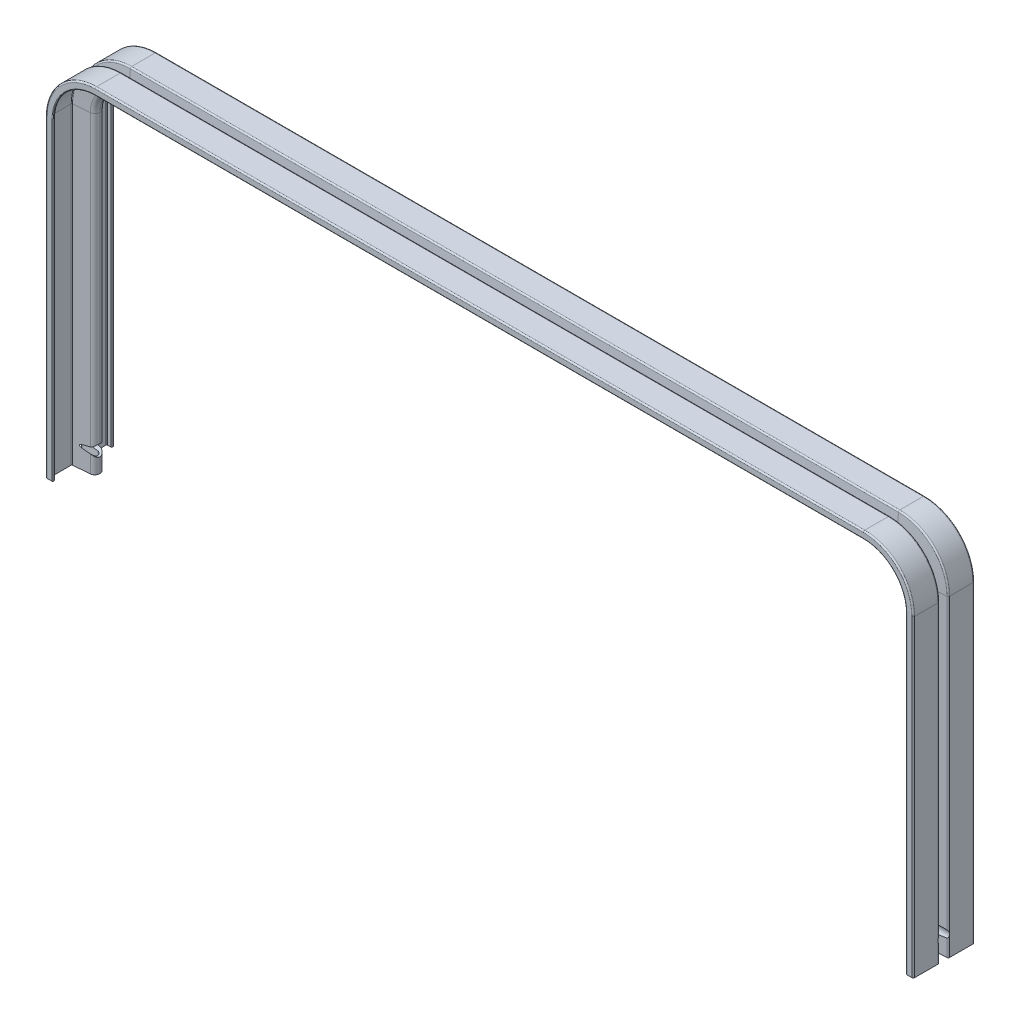
SolidWorks part; units mm, degrees
material "AISI 1020 Acero laminado en frío"
ref_plane "Alzado" through (0, 0, 0) normal (0, 0, 1) x (1, 0, 0)
ref_plane "Planta" through (0, 0, 0) normal (0, 1, 0) x (1, 0, 0)
ref_plane "Vista lateral" through (0, 0, 0) normal (1, 0, 0) x (0, 0, -1)
sketch "Croquis2" plane through (0, 0, 0) normal (1, 0, 0) x (0, 0, -1)
  line L4 (2, -2) -> (-2, -2) construction
  line L5 (21.5, 12) -> (-21.5, 12) construction
  line L8 (-3.5977, -0.2791) -> (-2.1024, -0.1595) construction
  line L9 (0, -3.5) -> (0, 12) construction
  line L10 (-3.0048, 11.1196) -> (-2.9952, 11)
  line L11 (-5.8278, 10.3021) -> (-7.826, 10.3021) construction
  line L12 (-5.8278, 10.3021) -> (-5.8278, 13.2411) construction
  line L13 (-5.8278, 13.2411) -> (-20.5, 13.2411)
  line L14 (-21.5, 12.2411) -> (-21.5, 8.7411)
  line L15 (-21, 8.2411) -> (-20.5, 8.2411)
  line L16 (-20, 8.7411) -> (-20, 11.2411)
  line L17 (-19.5, 11.7411) -> (-5.8278, 11.7411)
  line L18 (-4.5, 11) -> (-4.9298, 10.9656) construction
  line L19 (-4.5, 11) -> (-4.5881, 12.1007) construction
  line L20 (-5.8278, 11.7411) -> (-4.3336, 11.7411) construction
  line L21 (-4.5, 11) -> (-4.5225, 11.281)
  line L22 (-5.0209, 11.7411) -> (-5.8278, 11.7411)
  line L23 (-2.9952, 11) -> (-3.0048, 11.1196)
  line L24 (-3.0048, 11.1196) -> (-3.1009, 12.3209)
  line L25 (-5.8278, 13.2411) -> (-4.0977, 13.2411)
  line L26 (0.1088, -3.5) -> (-0.1088, -3.5)
  line L27 (-3.5977, -0.2791) -> (-4.5, 11)
  line L28 (-1.2335, -2) -> (-1.103, -2.2764) construction
  line L29 (-2.5488, 5.4203) -> (-1.7472, -4.6) construction
  line L30 (-1.236, -2) -> (-1.2335, -2)
  line L31 (-2.1024, -0.1595) -> (-2.9952, 11)
  line L32 (0.1088, -2) -> (-0.1088, -2)
  line L33 (-2.1024, -0.1595) -> (-2.9952, 11)
  line L34 (2.5488, 5.4203) -> (1.7472, -4.6) construction
  line L35 (1.2335, -2) -> (1.103, -2.2764) construction
  line L36 (5.8278, 11.7411) -> (4.3336, 11.7411) construction
  line L37 (4.5, 11) -> (4.5881, 12.1007) construction
  line L38 (4.5, 11) -> (4.9298, 10.9656) construction
  line L39 (5.8278, 10.3021) -> (5.8278, 13.2411) construction
  line L40 (5.8278, 10.3021) -> (7.826, 10.3021) construction
  line L41 (3.5977, -0.2791) -> (2.1024, -0.1595) construction
  line L42 (2.1024, -0.1595) -> (2.9952, 11)
  line L43 (2.1024, -0.1595) -> (2.9952, 11)
  line L44 (1.236, -2) -> (1.2335, -2)
  line L45 (3.5977, -0.2791) -> (4.5, 11)
  line L46 (5.8278, 13.2411) -> (4.0977, 13.2411)
  line L47 (3.0048, 11.1196) -> (3.1009, 12.3209)
  line L48 (2.9952, 11) -> (3.0048, 11.1196)
  line L49 (5.0209, 11.7411) -> (5.8278, 11.7411)
  line L50 (4.5, 11) -> (4.5225, 11.281)
  line L51 (19.5, 11.7411) -> (5.8278, 11.7411)
  line L52 (20, 8.7411) -> (20, 11.2411)
  line L53 (21, 8.2411) -> (20.5, 8.2411)
  line L54 (21.5, 12.2411) -> (21.5, 8.7411)
  line L55 (5.8278, 13.2411) -> (20.5, 13.2411)
  line L56 (3.0048, 11.1196) -> (2.9952, 11)
  arc A0 (-2.1024, -0.1595) -> (-0.1088, -2) centre (-0.1088, 0) ccw
  arc A1 (3.5977, -0.2791) -> (0.1088, -3.5) centre (0.1088, 0) cw
  arc A4 (-5.0209, 11.7411) -> (-4.5225, 11.281) centre (-5.0209, 11.2411) cw
  arc A5 (-3.1009, 12.3209) -> (-4.0977, 13.2411) centre (-4.0977, 12.2411) ccw
  arc A6 (-20, 11.2411) -> (-19.5, 11.7411) centre (-19.5, 11.2411) cw
  arc A7 (-20.5, 13.2411) -> (-21.5, 12.2411) centre (-20.5, 12.2411) ccw
  arc A8 (-20, 8.7411) -> (-20.5, 8.2411) centre (-20.5, 8.7411) cw
  arc A9 (-21, 8.2411) -> (-21.5, 8.7411) centre (-21, 8.7411) cw
  arc A10 (-3.5977, -0.2791) -> (-0.1088, -3.5) centre (-0.1088, 0) ccw
  arc A11 (21, 8.2411) -> (21.5, 8.7411) centre (21, 8.7411) ccw
  arc A12 (20, 8.7411) -> (20.5, 8.2411) centre (20.5, 8.7411) ccw
  arc A13 (20.5, 13.2411) -> (21.5, 12.2411) centre (20.5, 12.2411) cw
  arc A14 (20, 11.2411) -> (19.5, 11.7411) centre (19.5, 11.2411) ccw
  arc A15 (3.1009, 12.3209) -> (4.0977, 13.2411) centre (4.0977, 12.2411) cw
  arc A16 (5.0209, 11.7411) -> (4.5225, 11.281) centre (5.0209, 11.2411) ccw
  arc A17 (2.1024, -0.1595) -> (0.1088, -2) centre (0.1088, 0) cw
  point P4 (0, 0)
  point P8 (0, 12)
  point P32 (-4.5593, 11.7411)
  point P49 (-1.9552, -2)
  point P88 (0, -2)
  point P90 (1.9552, -2)
  point P91 (4.5593, 11.7411)
  dimension "D3" = 3.5
  dimension "D8" = 1.5
  dimension "D9" = 0.5
  dimension "D11" = 1
  dimension "D12" = 1.361
  dimension "D13" = 0.5
  dimension "D14" = 1
  dimension "D15" = 0.5
  dimension "D5" = 2
  dimension "D6" = 2
  dimension "D10" = 1.5
  dimension "D16" = 21.5
extrude "Saliente-Extruir1" add sketch "Croquis2" along normal mid plane 540 contours L42 A17 L32 A0 L31 L10 L24 A5 L25 L13 A7 L14 A9 L15 A8 L16 A6 L17 L22 A4 L21 L27 A10 L26 A1 L45 L50 A16 L49 L51 A14 L52 A12 L53 A11 L54 A13 L55 L46 A15 L47 L48 region at (0, 11.023, 3.46)
sketch "Croquis4" plane through (0, 0, 0) normal (0, 0, 1) x (1, 0, 0)
  line L0 (0, -4.7328) -> (0, 13.2411) construction
  line L1 (270, 13.2411) -> (-270, 13.2411) construction
  line L2 (0, 115.1283) -> (-251.0425, 15.746)
  line L3 (-270, -12.1478) -> (-270, -232.1463)
  line L4 (270, -12.1478) -> (270, -232.1463)
  line L5 (0, 115.1283) -> (251.0425, 15.746)
  arc A0 (-251.0425, 15.746) -> (-270, -12.1478) centre (-240, -12.1478) ccw
  arc A1 (251.0425, 15.746) -> (270, -12.1478) centre (240, -12.1478) cw
  point P10 (-270, 8.2411)
  point P15 (270, 8.2411)
  dimension "D1" = 30
  dimension "D2" = 269.9985
  dimension "D3" = 219.9985
sketch "Croquis9" plane through (270, 0, 0) normal (1, 0, 0) x (0, 0, -1)
  line L0 (-19.5, 11.7411) -> (-5.0209, 11.7411)
  line L1 (-4.5225, 11.281) -> (-3.5977, -0.2791)
  line L2 (-3.1009, 12.3209) -> (-2.1024, -0.1595)
  line L3 (2.1024, -0.1595) -> (3.1009, 12.3209)
  line L4 (4.5225, 11.281) -> (3.5977, -0.2791)
  line L5 (4.0977, 13.2411) -> (20.5, 13.2411)
  line L6 (21.5, 12.2411) -> (21.5, 8.7411)
  line L7 (21, 8.2411) -> (20.5, 8.2411)
  line L8 (21, 8.2411) -> (20.5, 8.2411) construction
  line L9 (20, 8.7411) -> (20, 11.2411)
  line L10 (19.5, 11.7411) -> (5.0209, 11.7411)
  line L11 (-20, 11.2411) -> (-20, 8.7411)
  line L12 (-20.5, 8.2411) -> (-21, 8.2411)
  line L13 (-21.5, 8.7411) -> (-21.5, 12.2411)
  line L14 (-20.5, 13.2411) -> (-4.0977, 13.2411)
  line L15 (-0.1088, -2) -> (0.1088, -2)
  line L16 (-0.1088, -3.5) -> (0.1088, -3.5)
  line L17 (-0.1088, -21.7589) -> (18.9384, -21.7589) construction
  arc A0 (21, 8.2411) -> (21.5, 8.7411) centre (21, 8.7411) ccw construction
  arc A1 (-21, 8.2411) -> (-21.5, 8.7411) centre (-21, 8.7411) cw
  arc A2 (-21.5, 12.2411) -> (-20.5, 13.2411) centre (-20.5, 12.2411) cw
  arc A3 (-20, 11.2411) -> (-19.5, 11.7411) centre (-19.5, 11.2411) cw
  arc A4 (-5.0209, 11.7411) -> (-4.5225, 11.281) centre (-5.0209, 11.2411) cw
  arc A5 (-4.0977, 13.2411) -> (-3.1009, 12.3209) centre (-4.0977, 12.2411) cw
  arc A6 (-3.5977, -0.2791) -> (-0.1088, -3.5) centre (-0.1088, 0) ccw
  arc A7 (-2.1024, -0.1595) -> (-0.1088, -2) centre (-0.1088, 0) ccw
  arc A8 (2.1024, -0.1595) -> (0.1088, -2) centre (0.1088, 0) cw
  arc A9 (3.5977, -0.2791) -> (0.1088, -3.5) centre (0.1088, 0) cw
  arc A10 (3.1009, 12.3209) -> (4.0977, 13.2411) centre (4.0977, 12.2411) cw
  arc A11 (4.5225, 11.281) -> (5.0209, 11.7411) centre (5.0209, 11.2411) cw
  arc A12 (19.5, 11.7411) -> (20, 11.2411) centre (19.5, 11.2411) cw
  arc A13 (20.5, 13.2411) -> (21.5, 12.2411) centre (20.5, 12.2411) cw
  arc A14 (20, 8.7411) -> (20.5, 8.2411) centre (20.5, 8.7411) ccw
  arc A15 (21, 8.2411) -> (21.5, 8.7411) centre (21, 8.7411) ccw
  arc A16 (-20.5, 8.2411) -> (-20, 8.7411) centre (-20.5, 8.7411) ccw
  dimension "D1" = 30
revolve "Revolución1" add sketch "Croquis9" angle 90 about L17
mirror "Simetría1" about plane through (0, 0, 0) normal (1, 0, 0) of "Revolución1"
sketch "Croquis10" plane through (0, -21.7589, 0) normal (0, -1, 0) x (1, 0, 0)
  line L0 (300.5, 21.5) -> (304, 21.5)
  line L1 (305, 20.5) -> (305, 4.0977)
  line L2 (300, 20.5) -> (300, 21)
  line L3 (300.5, 20) -> (303, 20)
  line L4 (303.5, 19.5) -> (303.5, 5.0209)
  line L5 (303.0399, 4.5225) -> (291.4798, 3.5977)
  line L6 (304.0797, 3.1009) -> (291.5994, 2.1024)
  line L7 (288.2589, -0.1088) -> (288.2589, 0.1088)
  line L8 (289.7589, -0.1088) -> (289.7589, 0.1088)
  line L9 (291.5994, -2.1024) -> (304.0797, -3.1009)
  line L10 (291.4798, -3.5977) -> (303.0399, -4.5225)
  line L11 (303.5, -19.5) -> (303.5, -5.0209)
  line L12 (305, -4.0977) -> (305, -20.5)
  line L13 (303, -20) -> (300.5, -20)
  line L14 (304, -21.5) -> (300.5, -21.5)
  line L15 (300, -21) -> (300, -20.5)
  arc A0 (304, 21.5) -> (305, 20.5) centre (304, 20.5) cw
  arc A1 (300.5, 21.5) -> (300, 21) centre (300.5, 21) ccw
  arc A2 (300, 20.5) -> (300.5, 20) centre (300.5, 20.5) ccw
  arc A3 (303, 20) -> (303.5, 19.5) centre (303, 19.5) cw
  arc A4 (303.5, 5.0209) -> (303.0399, 4.5225) centre (303, 5.0209) cw
  arc A5 (305, 4.0977) -> (304.0797, 3.1009) centre (304, 4.0977) cw
  arc A6 (291.4798, 3.5977) -> (288.2589, 0.1088) centre (291.7589, 0.1088) ccw
  arc A7 (291.5994, 2.1024) -> (289.7589, 0.1088) centre (291.7589, 0.1088) ccw
  arc A8 (288.2589, -0.1088) -> (291.4798, -3.5977) centre (291.7589, -0.1088) ccw
  arc A9 (289.7589, -0.1088) -> (291.5994, -2.1024) centre (291.7589, -0.1088) ccw
  arc A10 (303.5, -5.0209) -> (303.0399, -4.5225) centre (303, -5.0209) ccw
  arc A11 (304.0797, -3.1009) -> (305, -4.0977) centre (304, -4.0977) cw
  arc A12 (305, -20.5) -> (304, -21.5) centre (304, -20.5) cw
  arc A13 (303, -20) -> (303.5, -19.5) centre (303, -19.5) ccw
  arc A14 (300.5, -21.5) -> (300, -21) centre (300.5, -21) cw
  arc A15 (300, -20.5) -> (300.5, -20) centre (300.5, -20.5) cw
extrude "Saliente-Extruir2" add sketch "Croquis10" along normal blind 220
mirror "Simetría2" about plane through (0, 0, 0) normal (1, 0, 0) of "Saliente-Extruir2"
sketch "Croquis11" plane through (-305, 0, 0) normal (-1, 0, 0) x (0, 0, 1)
  line L0 (0.1088, -241.7589) -> (0.1088, -21.7589) construction
  circle A0 centre (0.1088, -227.4294) radius 4.05
  dimension "D1" = 8.1
extrude "Cortar-Extruir1" cut sketch "Croquis11" against normal through all
